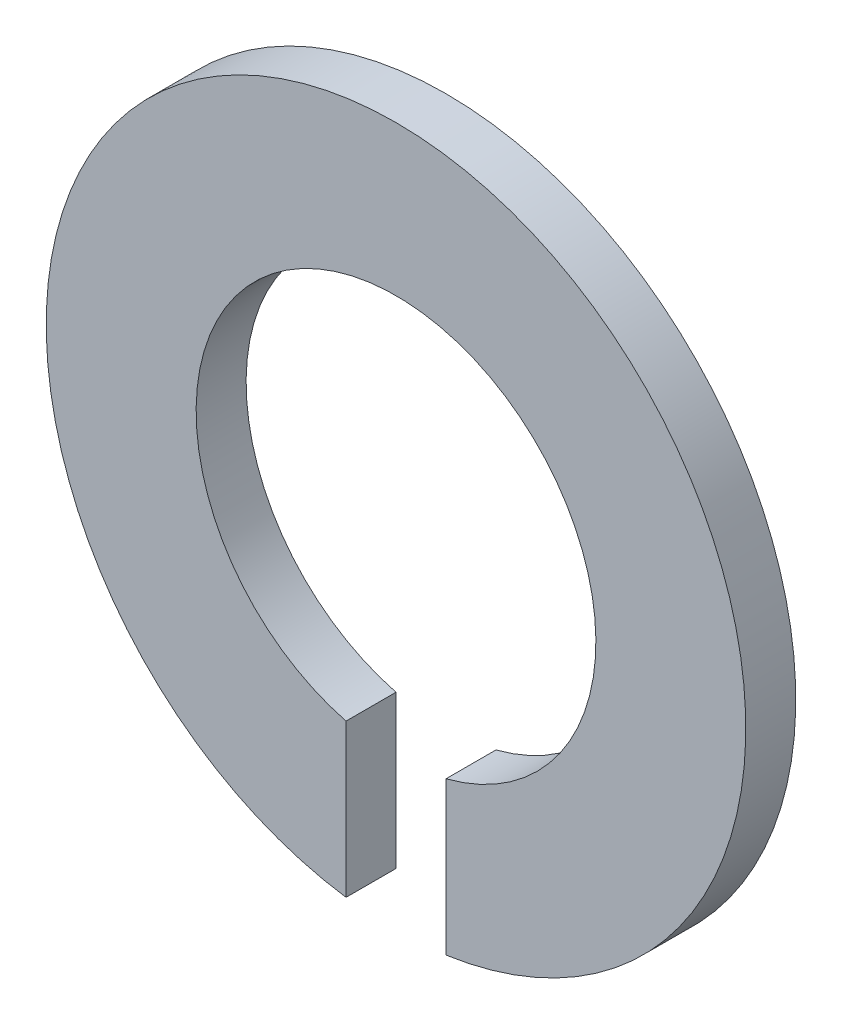
SolidWorks part; units mm, degrees
ref_plane "Plan de face" through (0, 0, 0) normal (0, 0, 1) x (1, 0, 0)
ref_plane "Plan de dessus" through (0, 0, 0) normal (0, 1, 0) x (1, 0, 0)
ref_plane "Plan de droite" through (0, 0, 0) normal (1, 0, 0) x (0, 0, -1)
sketch "Esquisse2" plane through (0, 0, 0) normal (0, 0, 1) x (1, 0, 0)
  line L0 (0, 0) -> (0, -4.3237) construction
  line L1 (0.5, -1.9365) -> (0.5, -3.4641)
  line L2 (-0.5, -1.9365) -> (-0.5, -3.4641)
  arc A0 (0.5, -3.4641) -> (-0.5, -3.4641) centre (0, 0) ccw
  arc A1 (0.5, -1.9365) -> (-0.5, -1.9365) centre (0, 0) ccw
  point P7 (0, 0)
  dimension "D1" = 7
  dimension "D2" = 4
  dimension "D3" = 0.5
extrude "Boss.-Extru.1" add sketch "Esquisse2" along normal blind 0.5
